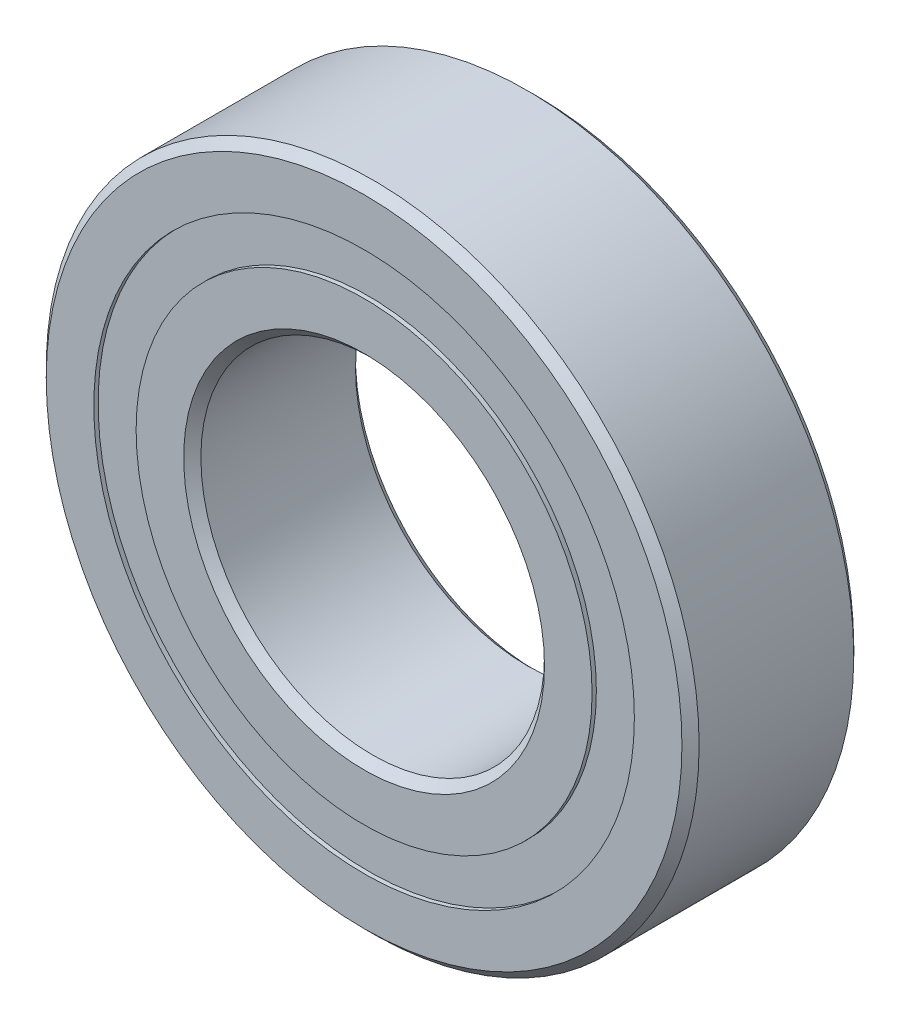
SolidWorks part; units mm, degrees
material "Alloy Steel"
ref_plane "Front Plane" through (0, 0, 0) normal (0, 0, 1) x (1, 0, 0)
ref_plane "Top Plane" through (0, 0, 0) normal (0, 1, 0) x (1, 0, 0)
ref_plane "Right Plane" through (0, 0, 0) normal (1, 0, 0) x (0, 0, -1)
sketch "Sketch1" plane through (0, 0, 0) normal (1, 0, 0) x (0, 0, -1)
  line L0 (-2.5, 0) -> (2.5, 0) construction
  line L1 (0, 9.5) -> (0, -9.5) construction
  line L2 (2.25, 9.5) -> (-2.25, 9.5)
  line L3 (-2.25, 9.5) -> (-2.5, 9.25)
  line L4 (-2.5, 9.25) -> (-2.5, 7.8654)
  line L5 (-2.5, 7.8654) -> (-1.1111, 7.8654)
  line L6 (2.5, 7.8654) -> (1.1111, 7.8654)
  line L7 (2.5, 9.25) -> (2.5, 7.8654)
  line L8 (2.25, 9.5) -> (2.5, 9.25)
  line L9 (0, 9.5) -> (0, 7.25) construction
  line L10 (0, 7.25) -> (0, 5) construction
  arc A0 (-1.1111, 7.8654) -> (1.1111, 7.8654) centre (0, 7.25) cw
  point P14 (0, 5)
  dimension "D3" = 2.2222
  dimension "D1" = 45
  dimension "Width" = 5
  dimension "OD" = 19
  dimension "D2" = 0.25
  dimension "Shaft Dia" = 10
  dimension "D4" = 0.6154
revolve "Revolve1" add sketch "Sketch1" angle 360 about L0
sketch "Sketch3" plane through (0, 0, 0) normal (1, 0, 0) x (0, 0, -1)
  line L0 (-2.5, 6.6346) -> (-1.1111, 6.6346)
  line L1 (0, 9.5) -> (0, -9.5) construction
  line L2 (-2.5, 9.25) -> (-2.5, 7.8654) construction
  line L3 (-2.5, 6.6346) -> (-2.5, 5.25)
  line L4 (-2.25, 9.5) -> (-2.5, 9.25) construction
  line L5 (-2.5, 5.25) -> (-2.25, 5)
  line L6 (-2.25, 5) -> (2.25, 5)
  line L7 (2.25, 9.5) -> (2.25, -9.5) construction
  line L8 (2.25, 5) -> (2.5, 5.25)
  line L9 (2.5, -9.25) -> (2.5, 9.25) construction
  line L10 (2.5, 5.25) -> (2.5, 6.6346)
  line L11 (2.5, 6.6346) -> (1.1111, 6.6346)
  line L13 (2.25, 9.5) -> (2.5, 9.25) construction
  arc A0 (1.1111, 7.8654) -> (-1.1111, 7.8654) centre (0, 7.25) ccw construction
  arc A1 (1.1111, 6.6346) -> (-1.1111, 6.6346) centre (0, 7.25) cw
revolve "Revolve3" add sketch "Sketch3" angle 360 about L0
sketch "Sketch4" plane through (0, 0, 0) normal (1, 0, 0) x (0, 0, -1)
  line L0 (-1.2701, 7.25) -> (1.2701, 7.25)
  arc A2 (-1.2701, 7.25) -> (1.2701, 7.25) centre (0, 7.25) cw
  arc A3 (1.1111, 7.8654) -> (-1.1111, 7.8654) centre (0, 7.25) ccw construction
revolve "Revolve4" add sketch "Sketch4" angle 360 about L0
ref_axis "Axis1" through (0, 0, -2.5) along (0, 0, 1)
pattern_circular "CirPattern1" count 12 every 30 about axis through (0, 0, -2.5) along (0, 0, 1) of bodies 104
sketch "Sketch5" plane through (0, 0, 0) normal (1, 0, 0) x (0, 0, -1)
  line L0 (-2.5, 7.8654) -> (-1.1111, 7.8654) construction
  line L1 (-2.375, 7.8654) -> (-1.2701, 7.8654)
  line L2 (-2.375, 7.8654) -> (-2.375, 6.6346)
  line L3 (-2.375, 6.6346) -> (-1.2701, 6.6346)
  line L4 (-1.2701, 7.8654) -> (-1.2701, 6.6346)
  line L5 (-2.5, 6.6346) -> (-1.1111, 6.6346) construction
  line L6 (2.5, 7.8654) -> (1.1111, 7.8654) construction
  line L7 (2.375, 7.8654) -> (1.2701, 7.8654)
  line L8 (2.375, 7.8654) -> (2.375, 6.6346)
  line L9 (2.375, 6.6346) -> (1.2701, 6.6346)
  line L10 (1.2701, 7.8654) -> (1.2701, 6.6346)
  line L11 (2.5, 6.6346) -> (1.1111, 6.6346) construction
  line L12 (-2.25, 9.5) -> (-2.5, 9.25) construction
  point P18 (-2.375, 9.375)
revolve "Revolve5" add sketch "Sketch5" angle 360 about L0
equation "\"D2@Sketch1\" = \"Width@Sketch1\"*.05"
equation "\"D3@Sketch1\" = \"Width@Sketch1\"/2.25"
equation "\"D4@Sketch1\" = (((\"OD@Sketch1\"-\"Width@Sketch1\")/2)/3.25)/3.5"
equation "\"D2@CirPattern1\" = 360/\"Balls@CirPattern1\""
